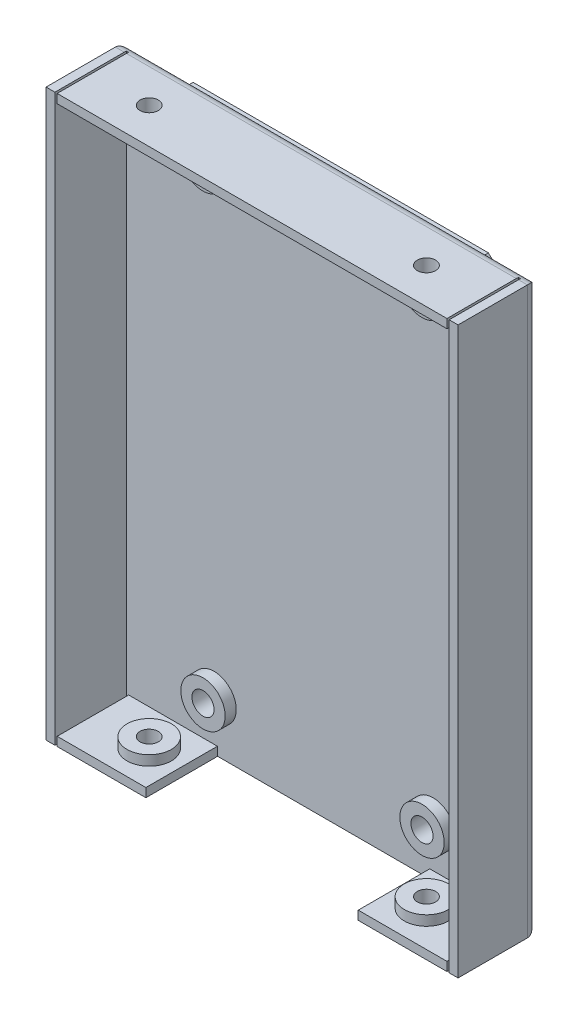
SolidWorks part; units mm, degrees
ref_plane "Front Plane" through (0, 0, 0) normal (0, 0, 1) x (1, 0, 0)
ref_plane "Top Plane" through (0, 0, 0) normal (0, 1, 0) x (1, 0, 0)
ref_plane "Right Plane" through (0, 0, 0) normal (1, 0, 0) x (0, 0, -1)
sketch "Sketch1" plane through (0, 0, 0) normal (0, 0, 1) x (1, 0, 0)
  line L1 (0, 0) -> (74.3, 0)
  line L2 (0, 0) -> (0, 102)
  line L3 (0, 102) -> (74.3, 102)
  line L4 (74.3, 0) -> (74.3, 102)
  dimension "D1" = 102
  dimension "D2" = 74.3
extrude "Boss-Extrude1" add sketch "Sketch1" along normal blind 1.6
sketch "Sketch2" plane through (0, 0, 1.6) normal (0, 0, 1) x (1, 0, 0)
  line L0 (0, 0) -> (74.3, 0) construction
  line L1 (0, 102) -> (1.6, 102)
  line L2 (0, 102) -> (0, 0)
  line L3 (0, 0) -> (1.6, 0)
  line L4 (1.6, 102) -> (1.6, 0)
  line L5 (37.15, 102) -> (37.15, 0) construction
  line L6 (74.3, 102) -> (0, 102) construction
  line L7 (74.3, 0) -> (72.7, 0)
  line L8 (74.3, 102) -> (72.7, 102)
  line L9 (72.7, 102) -> (72.7, 0)
  line L10 (74.3, 102) -> (74.3, 0)
  line L11 (72.3, 1.6) -> (56.3, 1.6)
  line L12 (2, 102) -> (72.3, 102)
  line L13 (2, 102) -> (2, 100.4)
  line L14 (2, 100.4) -> (72.3, 100.4)
  line L15 (72.3, 102) -> (72.3, 100.4)
  line L16 (2, 0) -> (18, 0)
  line L17 (2, 0) -> (2, 1.6)
  line L18 (2, 1.6) -> (18, 1.6)
  line L19 (18, 0) -> (18, 1.6)
  line L20 (56.3, 0) -> (56.3, 1.6)
  line L21 (72.3, 0) -> (56.3, 0)
  line L22 (72.3, 0) -> (72.3, 1.6)
  dimension "D1" = 1.6
  dimension "D2" = 0.4
  dimension "D3" = 0.4
  dimension "D4" = 1.6
  dimension "D5" = 16
  dimension "D6" = 1.6
  dimension "D7" = 0.4
extrude "Boss-Extrude2" add sketch "Sketch2" along normal blind 12.9
fillet "Fillet1" radius 2 4 edges at (0, 51, 0) (37.15, 0, 0) (74.3, 51, 0) (37.15, 102, 0)
sketch "Sketch3" plane through (0, 0, 1.6) normal (0, 0, 1) x (1, 0, 0)
  line L0 (37.15, 102) -> (37.15, 0.0404) construction
  line L1 (72.3, 102) -> (2, 102) construction
  line L2 (18, 0.0404) -> (56.3, 0.0404) construction
  line L3 (0, 51) -> (74.3, 51) construction
  line L4 (0, 102) -> (0, 0) construction
  line L5 (74.3, 0) -> (74.3, 102) construction
  line L6 (2, 0) -> (18, 0) construction
  circle A0 centre (17.4, 9) radius 4
  circle A1 centre (17.4, 9) radius 2
  circle A2 centre (56.9, 9) radius 4
  circle A3 centre (56.9, 9) radius 2
  circle A4 centre (56.9, 93) radius 2
  circle A5 centre (56.9, 93) radius 4
  circle A6 centre (17.4, 93) radius 2
  circle A7 centre (17.4, 93) radius 4
  dimension "D1" = 9
  dimension "D2" = 19.75
  dimension "D3" = 8
  dimension "D4" = 4
extrude "Boss-Extrude3" add sketch "Sketch3" along normal blind 2
extrude "Cut-Extrude1" cut sketch "Sketch3<3>" against normal blind 1.6 contours A6 | A4 | A3 | A1
sketch "Sketch3<3>" plane through (0, 0, 1.6) normal (0, 0, 1) x (1, 0, 0) same geometry as "Sketch3"
sketch "Sketch4" plane through (0, 0, 0) normal (0, 0, -1) x (-1, 0, 0)
  line L0 (-72.3, 102) -> (-2, 102) construction
  line L1 (-68.275, 100) -> (-6.025, 100)
  line L2 (-68.275, 100) -> (-68.275, 2.8)
  line L3 (-68.275, 2.8) -> (-6.025, 2.8)
  line L7 (-37.15, 102) -> (-37.15, 0.0404) construction
  line L8 (-18, 0.0404) -> (-56.3, 0.0404) construction
  line L9 (-6.025, 100) -> (-6.025, 2.8)
  line L10 (-6.025, 51.4) -> (-68.275, 51.4) construction
  line L11 (-22.65, 64.55) -> (-51.65, 64.55) construction
  line L12 (-22.65, 68.5) -> (-51.65, 68.5)
  line L13 (-22.65, 68.5) -> (-22.65, 60.6)
  line L14 (-22.65, 60.6) -> (-51.65, 60.6)
  line L15 (-51.65, 68.5) -> (-51.65, 60.6)
  line L16 (-22.65, 68.5) -> (-51.65, 60.6) construction
  line L17 (-22.65, 60.6) -> (-51.65, 68.5) construction
  line L18 (-55.55, 24.55) -> (-55.55, 64.55) construction
  circle A0 centre (-56.9, 93) radius 2
  circle A1 centre (-17.4, 93) radius 2
  circle A2 centre (-17.4, 9) radius 2
  circle A3 centre (-56.9, 9) radius 2
  circle A4 centre (-55.55, 64.55) radius 1.525
  circle A5 centre (-18.75, 64.55) radius 1.525
  circle A6 centre (-55.55, 24.55) radius 1.525
  circle A7 centre (-18.75, 24.55) radius 1.525
  point P10 (-37.15, 2.8)
  point P12 (-37.15, 100)
  point P26 (-37.15, 64.55)
  dimension "D7" = 3.05
  dimension "D1" = 31.125
  dimension "D2" = 97.2
  dimension "D3" = 2
  dimension "D4" = 31.5
  dimension "D5" = 29
  dimension "D6" = 7.9
  dimension "D8" = 3.9
  dimension "D9" = 40
extrude "Boss-Extrude4" add sketch "Sketch4" along normal blind 1.5 separate body
chamfer "Chamfer1" distance 4.5 4 edges at (6.025, 100, -0.75) (68.275, 100, -0.75) (68.275, 2.8, -0.75) (6.025, 2.8, -0.75)
sketch "Sketch5" plane through (0, 0, -1.5) normal (0, 0, -1) x (-1, 0, 0)
  line L0 (-37.15, 2.8) -> (-37.15, 100) construction
  line L1 (-63.775, 2.8) -> (-10.525, 2.8) construction
  line L2 (-10.525, 100) -> (-63.775, 100) construction
  line L3 (-68.275, 95.5) -> (-68.275, 7.3) construction
  circle A0 centre (-55.275, 45) radius 12.5
  circle A1 centre (-19.025, 45) radius 12.5
  dimension "D1" = 25
  dimension "D2" = 13
  dimension "D3" = 42.2
ref_plane "Plane1" through (0, 0, -4.1) normal (0, 0, -1) x (-1, 0, 0)
sketch "Sketch6" plane through (0, 0, -4.1) normal (0, 0, -1) x (-1, 0, 0)
  circle A0 centre (-55.275, 45) radius 8
  circle A1 centre (-19.025, 45) radius 8
  dimension "D1" = 16
loft "Loft1" add section "Sketch5" section "Sketch6" start constraint default connector at (49.6071, 33.8589, -1.5) connector at (54.5171, 37.036, -4.1)
ref_axis "Axis1" through (37.15, 100, -1.5) along (0, -0.9993, 0.038)
ref_plane "Plane2" through (37.15, 0, 0) normal (1, 0, 0) x (0, -0.9993, 0.038)
mirror "Mirror1" about plane through (37.15, 0, 0) normal (1, 0, 0) of "Loft1"
sketch "Sketch7" plane through (0, 0, -4.1) normal (0, 0, -1) x (-1, 0, 0)
  circle A0 centre (-55.275, 45) radius 8
  circle A1 centre (-19.025, 45) radius 8
  circle A2 centre (-55.275, 45) radius 6.75
  circle A3 centre (-19.025, 45) radius 6.75
  dimension "D1" = 13.5
extrude "Boss-Extrude5" add sketch "Sketch7" along normal blind 2.8
sketch "Sketch9" plane through (0, 1.6, 0) normal (0, 1, 0) x (1, 0, 0)
  line L0 (18, -8.05) -> (2, -8.05) construction
  line L1 (18, -14.5) -> (18, -1.6) construction
  line L2 (2, -14.5) -> (2, -1.6) construction
  circle A0 centre (12.15, -8.05) radius 4
  circle A1 centre (12.15, -8.05) radius 1.65
  dimension "D1" = 8
  dimension "D2" = 3.3
  dimension "D3" = 5.85
extrude "Cut-Extrude4" cut sketch "Sketch9" against normal through all contours A1
extrude "Boss-Extrude7" add sketch "Sketch9<6>" along normal blind 1.8
sketch "Sketch9<6>" plane through (0, 1.6, 0) normal (0, 1, 0) x (1, 0, 0) same geometry as "Sketch9"
mirror "Mirror2" about plane through (37.15, 0, 0) normal (1, 0, 0) of "Cut-Extrude4", "Boss-Extrude7"
ref_plane "Plane4" through (0, 51, 0) normal (0, 1, 0) x (1, 0, 0)
mirror "Mirror3" about plane through (0, 51, 0) normal (0, 1, 0) of "Cut-Extrude4", "Mirror2", "Boss-Extrude7"
